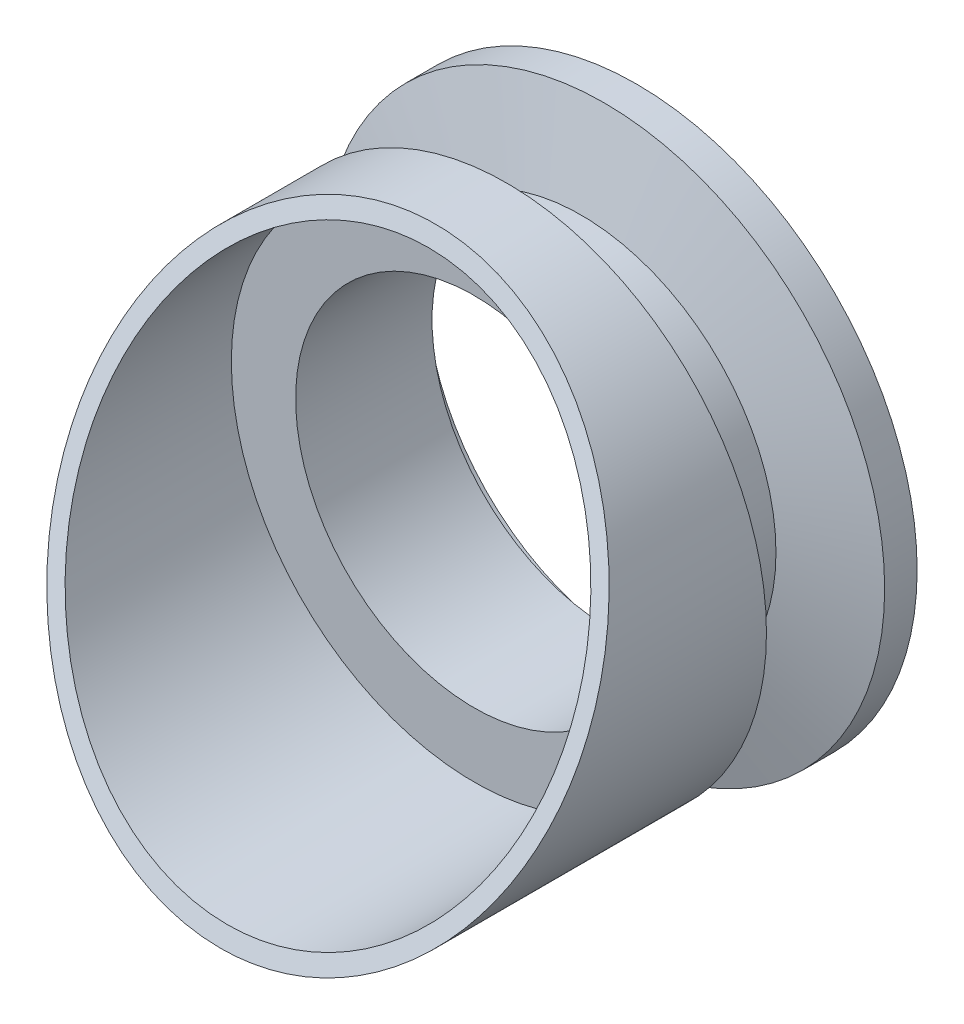
SolidWorks part; units mm, degrees
ref_plane "Front Plane" through (0, 0, 0) normal (0, 0, 1) x (1, 0, 0)
ref_plane "Top Plane" through (0, 0, 0) normal (0, 1, 0) x (1, 0, 0)
ref_plane "Right Plane" through (0, 0, 0) normal (1, 0, 0) x (0, 0, -1)
ref_axis "Axis1" through (0, 0, -97.7731) along (0, 0, 1)
sketch "Sketch9" plane through (0, 0, 0) normal (0, 0, 1) x (1, 0, 0)
  circle A0 centre (0, 0) radius 25.4
  circle A1 centre (0, 0) radius 23.7998
  dimension "D1" = 1.6002
  dimension "D2" = 50.8
sketch "Sketch2" plane through (0, 0, 0) normal (1, 0, 0) x (0, 0, -1)
  line L0 (0, 0) -> (22.225, 0)
  line L1 (22.225, 0) -> (73.025, -50.8)
  line L2 (73.025, -50.8) -> (87.3934, -65.1684)
  line L6 (73.025, -50.8) -> (87.3252, -50.8) construction
  dimension "D1" = 20.32
  dimension "D3" = 45
  dimension "D4" = 71.842
  dimension "D5" = 22.225
  dimension "D6" = 14.3002
  dimension "D7" = 50.8
sweep "Sweep1" [suppressed] add profiles "Sketch9" path "Sketch2"
sketch "Sketch12" [suppressed] plane through (0, 0, 0) normal (1, 0, 0) x (0, 0, -1)
  line L0 (-8.7619, 0) -> (-38.575, 0) construction
  line L1 (-8.7619, 40.2455) -> (7.9502, 40.2455)
  line L2 (-8.7619, 40.2455) -> (-8.7619, 24.9936)
  line L3 (-8.7619, 24.9936) -> (7.9502, 24.9936)
  line L4 (7.9502, 40.2455) -> (7.9502, 24.9936)
  dimension "D1" = 49.9872
  dimension "D2" = 7.9502
revolve "Cut-Revolve1" [suppressed] cut sketch "Sketch12" angle 360 about L0
sketch "Sketch11" [suppressed] plane through (0, 0, 0) normal (1, 0, 0) x (0, 0, -1)
  line L0 (88.8065, -12.7) -> (57.2435, -88.9)
  line L1 (57.2435, -88.9) -> (115.4775, -88.9)
  line L2 (115.4775, -88.9) -> (115.4775, -12.7)
  line L3 (115.4775, -12.7) -> (88.8065, -12.7)
  dimension "D1" = 22.5
  dimension "D2" = 76.2
extrude "Cut-Extrude2" [suppressed] cut sketch "Sketch11" against normal through all and the other way through all
sketch "Sketch4" plane through (0, 0, 0) normal (1, 0, 0) x (0, 0, -1)
  line L0 (87.3252, -33.3375) -> (100.6602, -33.3375)
  line L1 (100.6602, -33.3375) -> (100.6602, -30.226)
  line L2 (100.6602, -30.226) -> (103.2002, -30.226)
  line L3 (103.2002, -30.226) -> (103.2002, -23.368)
  line L4 (103.2002, -23.368) -> (100.0252, -23.368)
  line L5 (100.0252, -23.368) -> (97.7792, -31.75)
  line L6 (90.5002, -25.4) -> (58.7502, -25.4)
  line L7 (58.7502, -25.4) -> (58.7502, -27.051)
  line L8 (90.5002, -25.4) -> (90.5002, -31.75)
  line L9 (90.5002, -31.75) -> (97.7792, -31.75)
  line L11 (87.3252, -50.8) -> (149.1471, -50.8) construction
  line L13 (58.7502, -27.051) -> (87.3252, -27.051)
  line L14 (87.3252, -27.051) -> (87.3252, -33.3375)
  dimension "D1" = 34.925
  dimension "D2" = 54.864
  dimension "D3" = 50.8
  dimension "D4" = 38.1
  dimension "D5" = 15
  dimension "D6" = 2.54
  dimension "D7" = 3.175
  dimension "D8" = 1.651
  dimension "D9" = 3.175
  dimension "D10" = 12.7
  dimension "D11" = 6.858
  dimension "D12" = 44.45
  dimension "D13" = 41.148
revolve "Revolve2" add sketch "Sketch4" angle 360 about L11
sketch "Sketch10" plane through (0, 0, 0) normal (1, 0, 0) x (0, 0, -1)
  line L0 (57.4997, -88.2814) -> (88.5503, -13.3186)
  line L1 (88.5503, -13.3186) -> (35.3839, -13.3186)
  line L2 (35.3839, -13.3186) -> (35.3839, -88.2814)
  line L3 (35.3839, -88.2814) -> (57.4997, -88.2814)
  dimension "D1" = 22.5
extrude "Cut-Extrude1" cut sketch "Sketch10" against normal through all and the other way through all
fillet "Fillet1" [suppressed] radius 1.016
chamfer "Chamfer1" [suppressed] distance 0.381 angle 45
sketch "Sketch13" [suppressed] plane through (0, 0, 0) normal (1, 0, 0) x (0, 0, -1)
  line L0 (62.504, -76.2) -> (62.504, -45.4018)
  line L6 (83.546, -25.4) -> (62.504, -76.2) construction
  line L8 (62.504, -76.2) -> (89.4842, -76.2)
sketch "Sketch14" [suppressed] plane through (0, 0, 0) normal (1, 0, 0) x (0, 0, -1)
  line L0 (36.2606, 33.8849) -> (3.8151, -44.4454)
  line L1 (3.8151, -44.4454) -> (58.5788, -85.6763)
  line L2 (58.5788, -85.6763) -> (95.6091, 3.7228)
  line L3 (12.3668, -23.7998) -> (32.0832, 23.7998) construction
  line L4 (63.1668, -74.5998) -> (82.8832, -27.0002) construction
